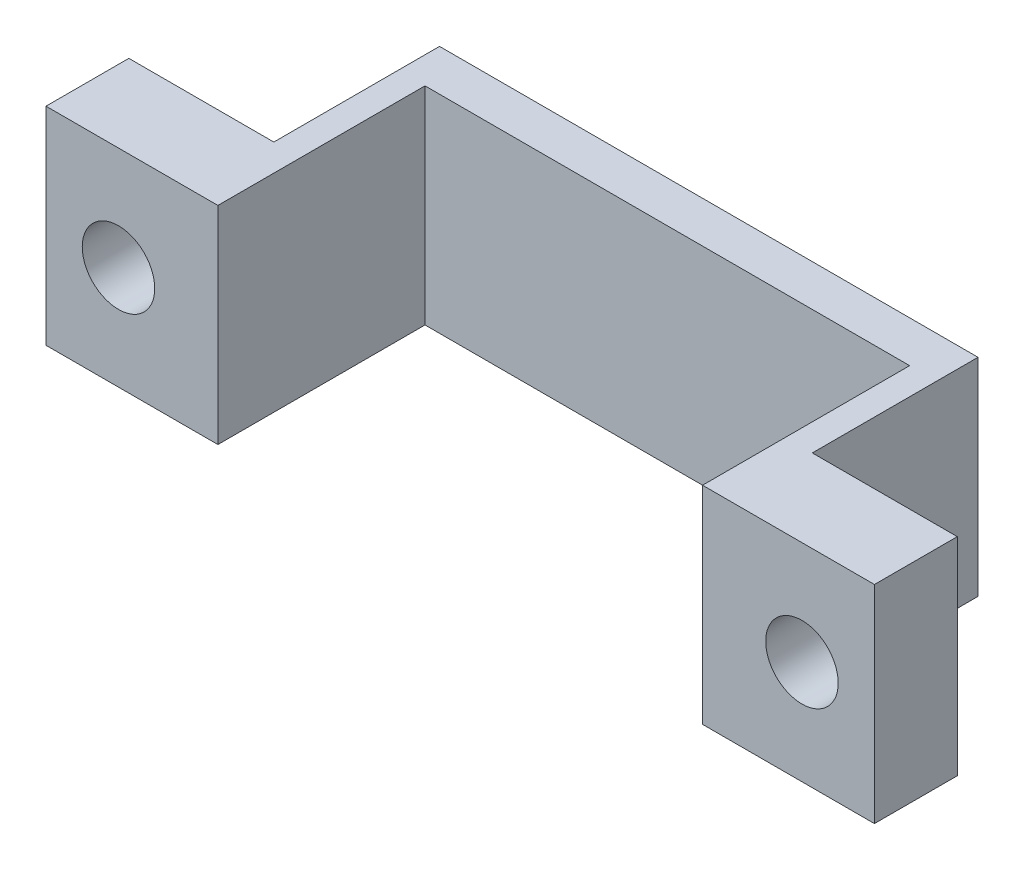
SolidWorks part; units mm, degrees
ref_plane "Спереди" through (0, 0, 0) normal (0, 0, 1) x (1, 0, 0)
ref_plane "Сверху" through (0, 0, 0) normal (0, 1, 0) x (1, 0, 0)
ref_plane "Справа" through (0, 0, 0) normal (1, 0, 0) x (0, 0, -1)
sketch "Эскиз1" plane through (0, 0, 0) normal (0, 1, 0) x (1, 0, 0)
  line L0 (-13, 2) -> (13, 2)
  line L1 (13, 2) -> (13, -6)
  line L2 (-13, 2) -> (-13, -6)
  line L3 (13, -6) -> (20, -6)
  line L4 (-13, -6) -> (-20, -6)
  line L5 (20, -6) -> (20, -10)
  line L6 (-20, -6) -> (-20, -10)
  line L7 (-20, -10) -> (-11.7, -10)
  line L8 (20, -10) -> (11.7, -10)
  line L9 (11.7, -10) -> (11.7, 0)
  line L10 (-11.7, -10) -> (-11.7, 0)
  line L11 (-11.7, 0) -> (11.7, 0)
  line L12 (15.85, -7.2854) -> (15.85, -8.9156) construction
  line L13 (-15.85, -7.2854) -> (-15.85, -9.2854) construction
  point P12 (0, 0)
  dimension "D1" = 26
  dimension "D2" = 8
  dimension "D3" = 8
  dimension "D4" = 7
  dimension "D5" = 7
  dimension "D6" = 4
  dimension "D7" = 4
  dimension "D8" = 8.3
  dimension "D9" = 8.3
  dimension "D10" = 2
  dimension "D11" = 4.15
  dimension "D12" = 2
  dimension "D13" = 4.15
  dimension "D14" = 31.7
extrude "Бобышка-Вытянуть1" add sketch "Эскиз1" along normal blind 10
ref_plane "Плоскость1" through (0, 0, 0) normal (-1, 0, 0) x (0, 0, 1)
sketch "Эскиз3" plane through (0, 0, 6) normal (0, 0, -1) x (-1, 0, 0)
  line L0 (20, 5) -> (-20, 5) construction
  line L1 (20, 10) -> (20, 0) construction
  line L2 (-20, 10) -> (-20, 0) construction
  line L3 (16.5, 10) -> (16.5, 0) construction
  line L4 (13, 10) -> (20, 10) construction
  line L5 (13, 0) -> (20, 0) construction
  circle A0 centre (16.5, 5) radius 1.75
  dimension "D1" = 3.5
extrude "Вырез-Вытянуть2" cut sketch "Эскиз3" against normal blind 4
mirror "Зеркальное отражение1" about plane through (0, 0, 0) normal (-1, 0, 0) of "Вырез-Вытянуть2"
